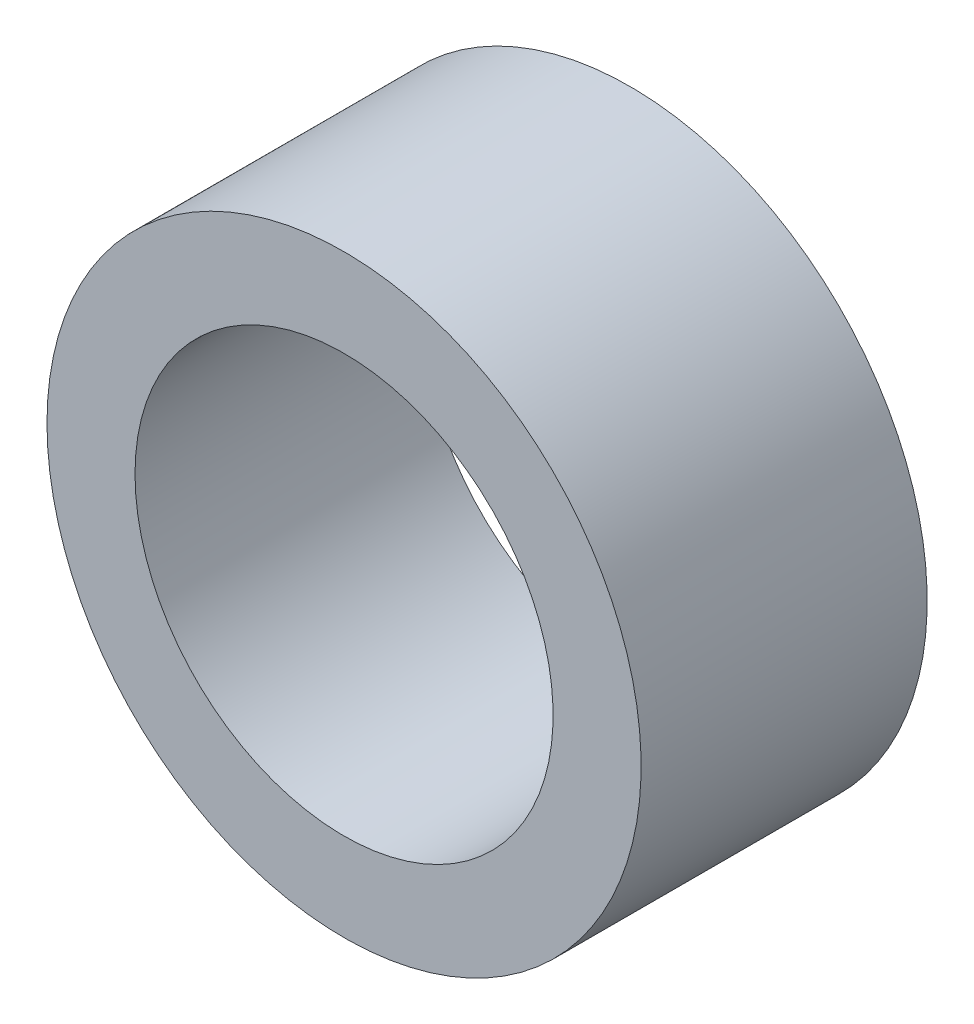
SolidWorks part; units mm, degrees
material "Caucho de silicio"
ref_plane "Alzado" through (0, 0, 0) normal (0, 0, 1) x (1, 0, 0)
ref_plane "Planta" through (0, 0, 0) normal (0, 1, 0) x (1, 0, 0)
ref_plane "Vista lateral" through (0, 0, 0) normal (1, 0, 0) x (0, 0, -1)
sketch "Croquis1" plane through (0, 0, 0) normal (0, 0, 1) x (1, 0, 0)
  circle A0 centre (0, 0) radius 19
  circle A1 centre (0, 0) radius 27
  dimension "D1" = 54
  dimension "D2" = 38
extrude "Saliente-Extruir1" add sketch "Croquis1" along normal blind 26
